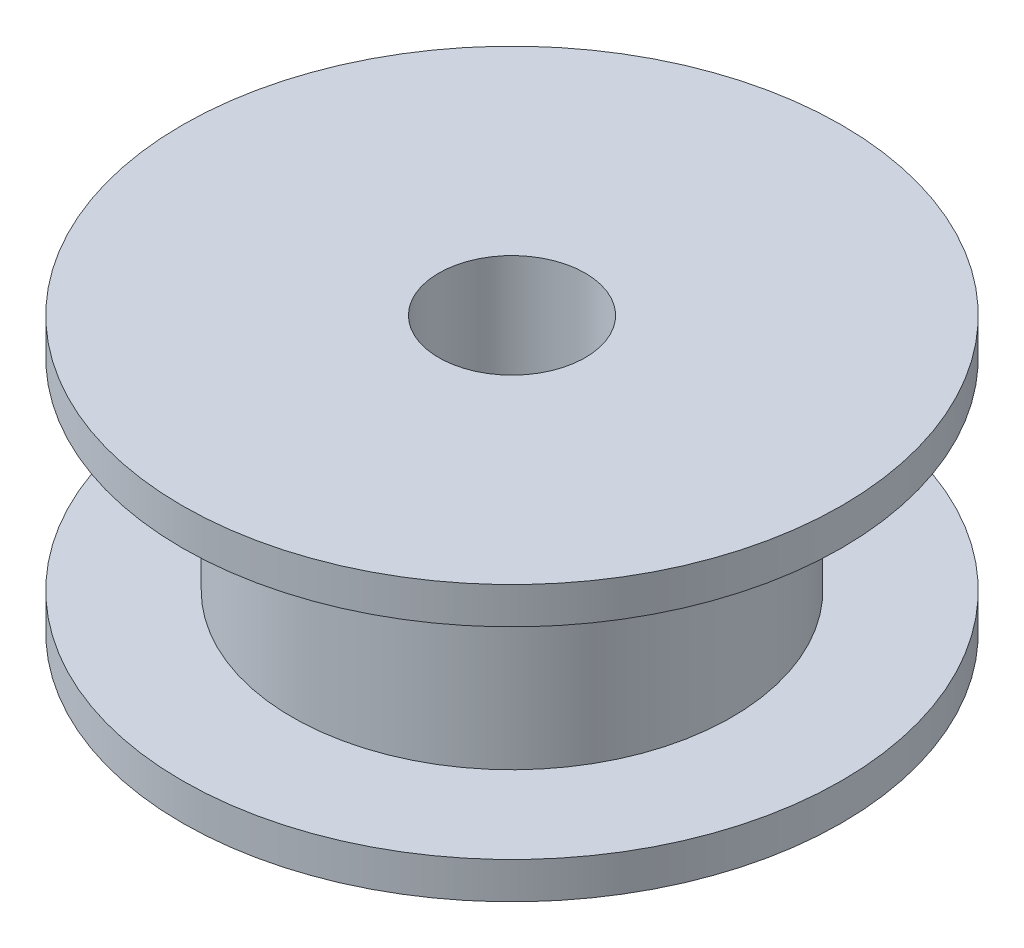
SolidWorks part; units mm, degrees
ref_plane "Ebene vorne" through (0, 0, 0) normal (0, 0, 1) x (1, 0, 0)
ref_plane "Ebene oben" through (0, 0, 0) normal (0, 1, 0) x (1, 0, 0)
ref_plane "Ebene rechts" through (0, 0, 0) normal (1, 0, 0) x (0, 0, -1)
sketch "Skizze1" plane through (0, 0, 0) normal (0, 1, 0) x (1, 0, 0)
  circle A0 centre (0, 0) radius 9
  circle A1 centre (0, 0) radius 6
  circle A2 centre (0, 0) radius 2
  dimension "D1" = 18
  dimension "D2" = 12
  dimension "D3" = 4
extrude "Aufsatz-Linear austragen1" add sketch "Skizze1" along normal blind 1 contours A0 A1 region at (-8.7454, 0, 0)
extrude "Aufsatz-Linear austragen2" add sketch "Skizze1<3>" along normal blind 6.5 contours A1 A2 region at (-5.8303, 0, 0)
sketch "Skizze1<3>" plane through (0, 0, 0) normal (0, 1, 0) x (1, 0, 0) same geometry as "Skizze1"
sketch "Skizze2" plane through (0, 6.5, 0) normal (0, 1, 0) x (1, 0, 0)
  circle A0 centre (0, 0) radius 2
  circle A1 centre (0, 0) radius 9
extrude "Aufsatz-Linear austragen3" add sketch "Skizze2" along normal blind 1
